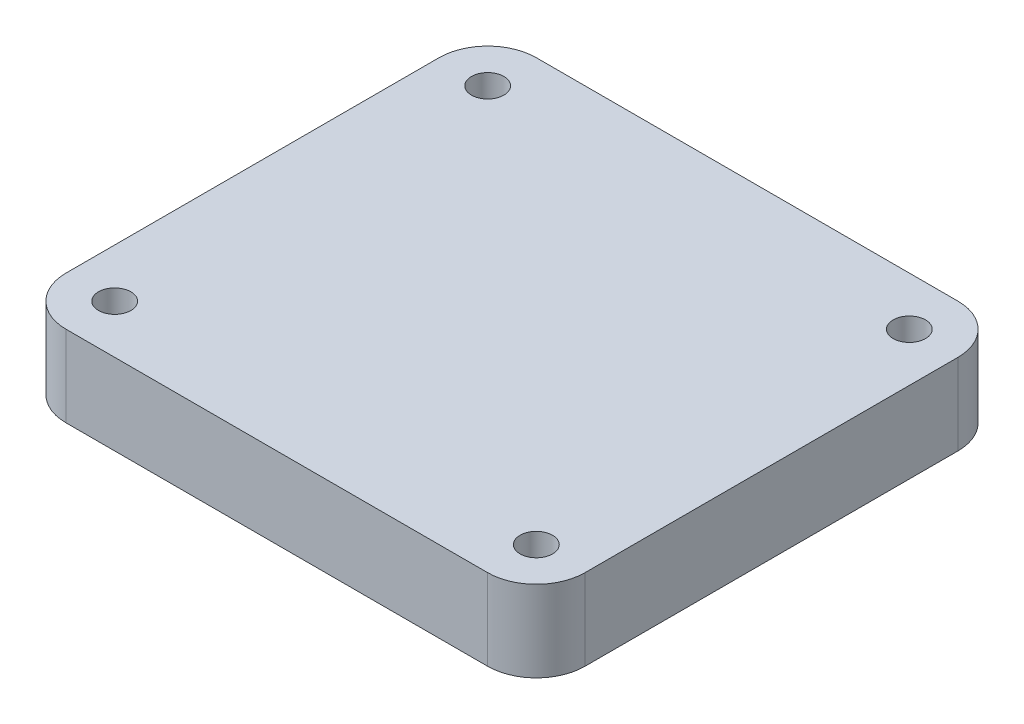
SolidWorks part; units mm, degrees
material "ABS"
ref_plane "Спереди" through (0, 0, 0) normal (0, 0, 1) x (1, 0, 0)
ref_plane "Сверху" through (0, 0, 0) normal (0, 1, 0) x (1, 0, 0)
ref_plane "Справа" through (0, 0, 0) normal (1, 0, 0) x (0, 0, -1)
sketch "Эскиз1" plane through (0, 0, 0) normal (0, 1, 0) x (1, 0, 0)
  line L0 (0, 29) -> (0, -29) construction
  line L1 (-26, 29) -> (26, 29)
  line L2 (-32, 23) -> (-32, -23)
  line L3 (-26, -29) -> (26, -29)
  line L4 (32, 23) -> (32, -23)
  line L5 (-32, 0) -> (32, 0) construction
  line L16 (7.75, 26) -> (-16.75, 26)
  line L17 (-29, 13.75) -> (-29, -13.75)
  line L18 (-7.75, -26) -> (16.75, -26)
  line L19 (29, 13.75) -> (29, -13.75)
  line L20 (-26, 23) -> (-19.75, 23) construction
  line L21 (-26, 23) -> (-26, 16.75) construction
  line L22 (26, 16.75) -> (17, 16.75)
  line L24 (-26, -16.75) -> (-17, -16.75)
  line L40 (17, 18.75) -> (23.3661, 18.75)
  line L41 (22.637, 26.7) -> (11.113, 26.7)
  line L44 (-22.637, -26.7) -> (-11.113, -26.7)
  line L45 (-17, -18.75) -> (-23.3661, -18.75)
  circle A14 centre (-26, 23) radius 2
  circle A15 centre (26, 23) radius 2
  circle A16 centre (26, -23) radius 2
  circle A17 centre (-26, -23) radius 2
  arc A18 (-26, 29) -> (-32, 23) centre (-26, 23) ccw
  arc A19 (26, 29) -> (32, 23) centre (26, 23) cw
  arc A20 (26, -29) -> (32, -23) centre (26, -23) ccw
  arc A21 (-26, -29) -> (-32, -23) centre (-26, -23) cw
  arc A22 (-19.75, 23) -> (-26, 16.75) centre (-26, 23) cw
  arc A23 (-16.75, 26) -> (-19.75, 23) centre (-16.75, 23) ccw
  arc A24 (-26, 16.75) -> (-29, 13.75) centre (-26, 13.75) ccw
  arc A25 (19.75, -23) -> (26, -16.75) centre (26, -23) cw
  arc A26 (26, -16.75) -> (29, -13.75) centre (26, -13.75) ccw
  arc A27 (16.75, -26) -> (19.75, -23) centre (16.75, -23) ccw
  arc A28 (10.75, 23) -> (7.75, 26) centre (7.75, 23) ccw
  arc A29 (17, 16.75) -> (10.75, 23) centre (17, 23) cw
  arc A30 (26, 16.75) -> (29, 13.75) centre (26, 13.75) cw
  arc A31 (-26, -16.75) -> (-29, -13.75) centre (-26, -13.75) cw
  arc A32 (-17, -16.75) -> (-10.75, -23) centre (-17, -23) cw
  arc A34 (-10.75, -23) -> (-7.75, -26) centre (-7.75, -23) ccw
  arc A46 (12.75, 23) -> (17, 18.75) centre (17, 23) ccw
  arc A47 (22.637, 26.7) -> (23.3661, 18.75) centre (26, 23) ccw
  arc A48 (12.75, 23) -> (11.113, 26.7) centre (7.75, 23) ccw
  arc A52 (-22.637, -26.7) -> (-23.3661, -18.75) centre (-26, -23) ccw
  arc A53 (-12.75, -23) -> (-11.113, -26.7) centre (-7.75, -23) ccw
  arc A54 (-12.75, -23) -> (-17, -18.75) centre (-17, -23) ccw
  point P63 (-29, 0)
  point P127 (-30.2426, 27.2426)
  dimension "D9" = 4
  dimension "D17" = 6
  dimension "D18" = 30.5
  dimension "D16" = 3
  dimension "D14" = 33.5
  dimension "D19" = 33.5
  dimension "D15" = 3
  dimension "D26" = 3
  dimension "D27" = 2
  dimension "D28" = 2
  dimension "D1" = 64
  dimension "D2" = 58
  dimension "D10" = 52
  dimension "D11" = 46
  dimension "D12" = 58
  dimension "D13" = 52
  dimension "D29" = 2
  dimension "D30" = 2.3
  dimension "D31" = 2.3
extrude "Бобышка-Вытянуть1" add sketch "Эскиз1" along normal blind 10
extrude "Бобышка-Вытянуть3" add sketch "Эскиз1<15>" against normal blind 3 from surface contours A32 A34 L18 A27 A25 A26 L19 A30 L22 A29 A28 L16 A23 A22 A24 L17 A31 L24 | A48 A46 L40 A47 L41 | A53 A54 L45 A52 L44 region at (0, 0, 0) region at (17.2619, 0, -22.9364) region at (-17.2619, 0, 22.9364) starting at face at (16.8792, 10, -22.6022)
sketch "Эскиз1<15>" plane through (0, 0, 0) normal (0, 1, 0) x (1, 0, 0) same geometry as "Эскиз1"
